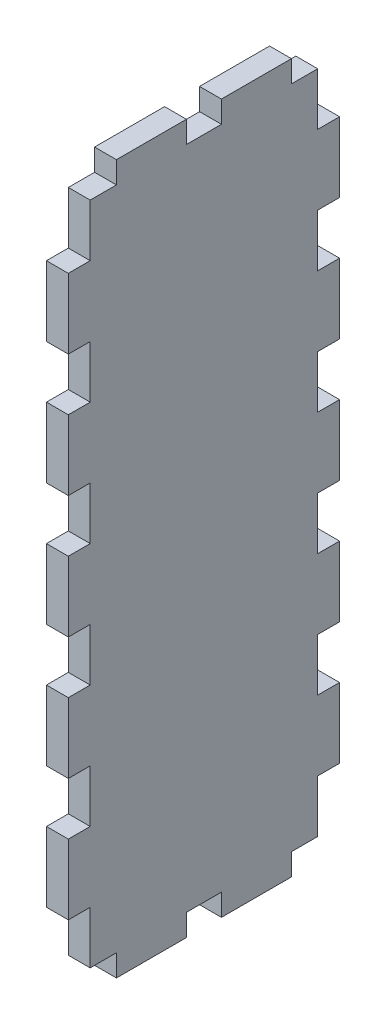
SolidWorks part; units mm, degrees
ref_plane "Front Plane" through (0, 0, 0) normal (0, 0, 1) x (1, 0, 0)
ref_plane "Top Plane" through (0, 0, 0) normal (0, 1, 0) x (1, 0, 0)
ref_plane "Right Plane" through (0, 0, 0) normal (1, 0, 0) x (0, 0, -1)
sketch "Sketch1" plane through (0, 0, 0) normal (1, 0, 0) x (0, 0, -1)
  line L1 (-16.0286, 45.908) -> (16.9914, 45.908)
  line L2 (-16.0286, 45.908) -> (-16.0286, -50.612)
  line L3 (-16.0286, -50.612) -> (16.9914, -50.612)
  line L4 (16.9914, 45.908) -> (16.9914, -50.612)
  dimension "D1" = 96.52
  dimension "D2" = 33.02
extrude "Boss-Extrude1" add sketch "Sketch1" along normal blind 3.175
sketch "Sketch2" plane through (0, 0, 0) normal (-1, 0, 0) x (0, 0, 1)
  line L0 (16.0286, 45.908) -> (16.0286, 38.288) construction
  line L1 (16.0286, 45.908) -> (16.0286, -50.612) construction
  dimension "D1" = 7.62
sketch "Sketch3" plane through (0, 0, 16.0286) normal (0, 0, 1) x (1, 0, 0)
  line L0 (3.175, 45.908) -> (3.175, -50.612) construction
  line L1 (0, 38.288) -> (3.175, 38.288)
  line L2 (0, 38.288) -> (0, 28.128)
  line L3 (0, 28.128) -> (3.175, 28.128)
  line L4 (3.175, 38.288) -> (3.175, 28.128)
  dimension "D1" = 10.16
extrude "Boss-Extrude2" add sketch "Sketch3" along normal blind 3.175
pattern_linear "LPattern1" count 5 spacing 17.78 along (0, -1, 0) of "Boss-Extrude2"
ref_plane "Plane1" through (0, 0, -0.4814) normal (0, 0, -1) x (-1, 0, 0)
mirror "Mirror1" about plane through (0, 0, -0.4814) normal (0, 0, -1) of "LPattern1"
ref_plane "Plane3" through (0, -2.352, 0) normal (0, 1, 0) x (1, 0, 0)
sketch "Sketch4" plane through (0, 45.908, 0) normal (0, 1, 0) x (1, 0, 0)
  line L0 (0, -16.0286) -> (0, -12.2186) construction
  line L1 (0, 16.9914) -> (0, -16.0286) construction
  line L2 (0, 16.9914) -> (0, 13.1814) construction
  line L3 (3.175, 16.9914) -> (3.175, -16.0286) construction
  line L4 (0, -12.2186) -> (3.175, -12.2186)
  line L5 (0, -12.2186) -> (0, -2.0586)
  line L6 (0, -2.0586) -> (3.175, -2.0586)
  line L7 (3.175, -12.2186) -> (3.175, -2.0586)
  dimension "D1" = 3.81
  dimension "D2" = 3.81
  dimension "D3" = 10.16
extrude "Boss-Extrude3" add sketch "Sketch4" along normal blind 3.175
mirror "Mirror2" about plane through (0, 0, -0.4814) normal (0, 0, -1) of "Boss-Extrude3"
mirror "Mirror3" about plane through (0, -2.352, 0) normal (0, 1, 0) of "Mirror2"
sketch "Sketch5" plane through (0, 0, 0) normal (-1, 0, 0) x (0, 0, 1)
  line L2 (-10.0175, 27.109) -> (-10.0175, -41.9091)
  line L3 (-10.0175, -41.9091) -> (9.3334, -41.9091)
  line L4 (9.3334, 27.109) -> (9.3334, -41.9091)
  spline S0 degree 3 poles (-10.0175, 27.109) (-4.5742, 32.181) (1.8741, 32.8383) (9.3334, 27.109) knots 0 0 0 0 1 1 1 1
